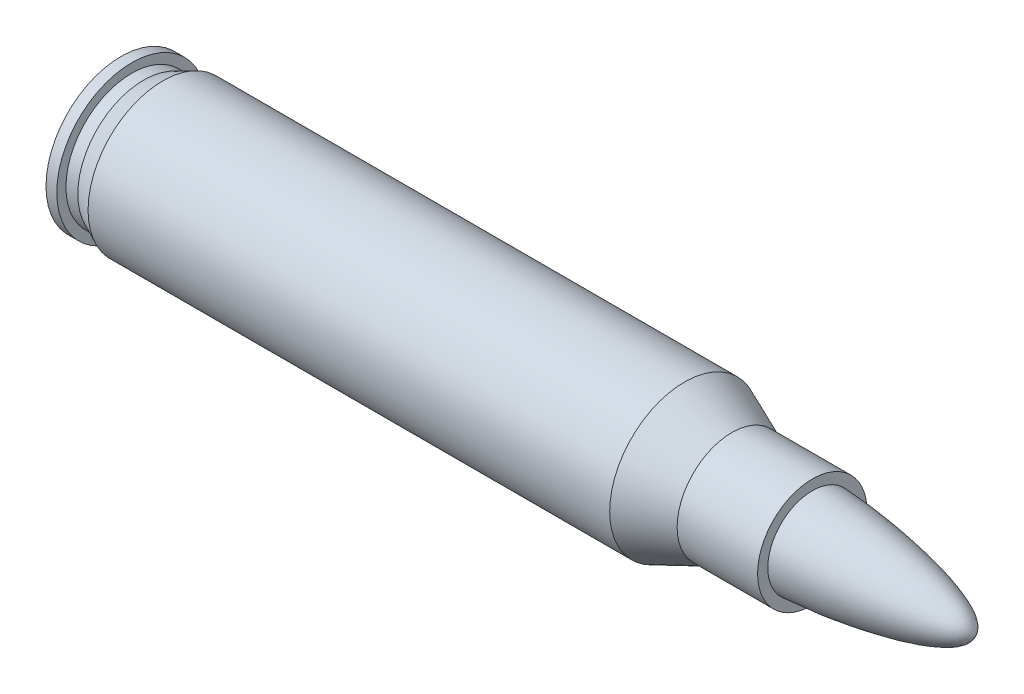
SolidWorks part; units mm, degrees
ref_plane "Front Plane" through (0, 0, 0) normal (0, 0, 1) x (1, 0, 0)
ref_plane "Top Plane" through (0, 0, 0) normal (0, 1, 0) x (1, 0, 0)
ref_plane "Right Plane" through (0, 0, 0) normal (1, 0, 0) x (0, 0, -1)
sketch "Sketch4" plane through (0, 0, 0) normal (0, 1, 0) x (1, 0, 0)
  line L0 (36.52, 4.7886) -> (36.52, 0)
  line L1 (0, 0) -> (0, 4.1573)
  line L2 (0, 4.1573) -> (0.45, 4.8)
  line L3 (0.45, 4.8) -> (1.14, 4.8)
  line L4 (1.14, 4.8) -> (1.14, 4.215)
  line L5 (1.14, 4.215) -> (1.9, 4.215)
  line L6 (1.9, 4.215) -> (3.13, 4.7886)
  line L7 (3.13, 4.7886) -> (36.52, 4.7886)
  line L8 (36.52, 4.7886) -> (39.55, 3.5024)
  line L9 (39.55, 3.5024) -> (44.7, 3.5024)
  line L10 (44.7, 3.5024) -> (44.7, 2.85)
  line L11 (0, 0) -> (55.0428, 0)
  line L12 (39.55, 3.5024) -> (39.55, 0)
  line L13 (44.7, 2.85) -> (44.7, 0)
  spline S0 degree 3 poles (44.7, 2.85) (45.6959, 2.8022) (47.1132, 2.6655) (49.0264, 2.3857) (50.9897, 2.036) (52.835, 1.5882) (54.2231, 0.9818) (54.6593, 0.6627) (54.9007, 0.3783) (55.0123, 0.1539) (55.0428, 0) knots 0 0 0 0 0.270565 0.386221 0.524695 0.812072 0.899191 0.933555 0.957542 1 1 1 1
  point P14 (55.0428, 0)
  point P18 (55.0107, 0.1189)
  dimension "D13" = 2.85
  dimension "D1" = 0.45
  dimension "D2" = 35
  dimension "D3" = 4.8
  dimension "D4" = 4.215
  dimension "D5" = 25
  dimension "D6" = 1.14
  dimension "D7" = 0.76
  dimension "D8" = 3.13
  dimension "D9" = 23
  dimension "D10" = 44.7
  dimension "D11" = 39.55
  dimension "D12" = 36.52
revolve "Revolve1" add sketch "Sketch4" angle 360 about L11 region at (37.9567, 0, -2.0894) region at (18.348, 0, -2.3829) region at (42.125, 0, -1.7512) region at (48.9547, 0, -1.1386)
